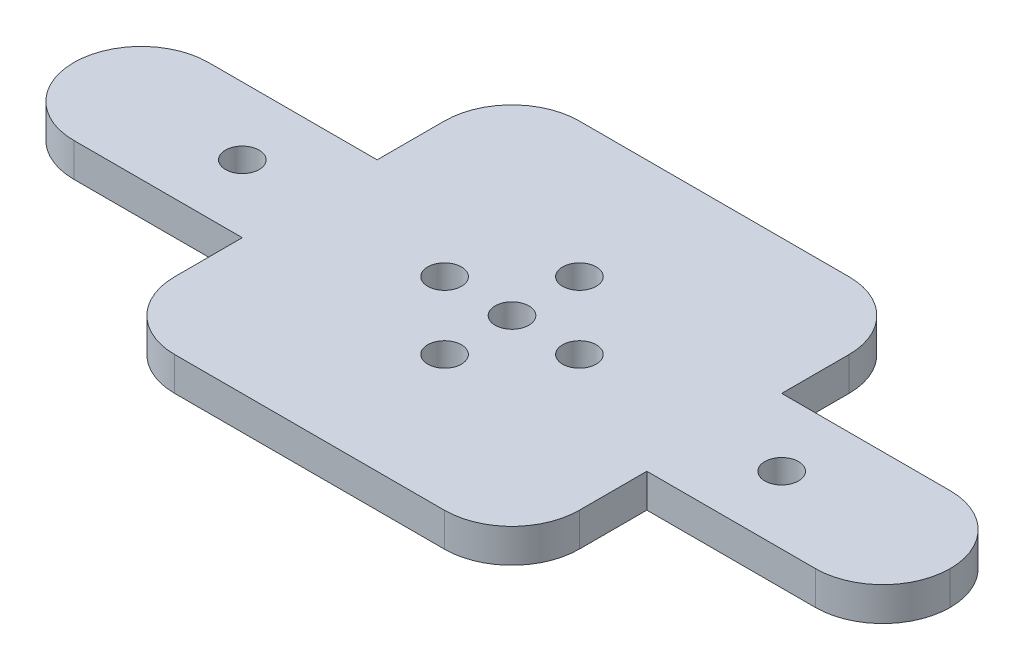
SolidWorks part; units mm, degrees
ref_plane "Front Plane" through (0, 0, 0) normal (0, 0, 1) x (1, 0, 0)
ref_plane "Top Plane" through (0, 0, 0) normal (0, 1, 0) x (1, 0, 0)
ref_plane "Right Plane" through (0, 0, 0) normal (1, 0, 0) x (0, 0, -1)
sketch "Sketch1" plane through (0, 0, 0) normal (0, 1, 0) x (1, 0, 0)
  line L0 (69.4221, 30.0207) -> (-16.2022, 30.0207) construction
  line L1 (0, 0) -> (60, 0)
  line L2 (0, 0) -> (0, 60)
  line L3 (0, 60) -> (60, 60)
  line L4 (60, 0) -> (60, 60)
  line L5 (30, 63.9004) -> (30, -4.8431) construction
  line L6 (23.4653, 40.0207) -> (37.3207, 40.0207) construction
  line L7 (20, 36.8255) -> (20, 23.5223) construction
  line L8 (23.8167, 20.0207) -> (36.7183, 20.0207) construction
  line L9 (40, 25.4802) -> (40, 39.2352) construction
  line L10 (64.811, 30) -> (-8.1915, 30) construction
  circle A0 centre (30, 40.0207) radius 2.5
  circle A1 centre (20, 30.0207) radius 2.5
  circle A2 centre (30, 20.0207) radius 2.5
  circle A3 centre (40, 30.0207) radius 2.5
  circle A4 centre (30, 30.0207) radius 2.5
  dimension "D3" = 5
  dimension "D4" = 5
  dimension "D5" = 5
  dimension "D6" = 5
  dimension "D11" = 5
  dimension "D1" = 60
  dimension "D2" = 60
  dimension "D7" = 10
  dimension "D8" = 10
  dimension "D9" = 10
  dimension "D10" = 10
extrude "Boss-Extrude2" add sketch "Sketch1" along normal blind 5
sketch "Sketch3" plane through (0, 0, 0) normal (0, 1, 0) x (1, 0, 0)
  line L0 (73.9499, 30) -> (-18.7239, 30) construction
  line L1 (30, 64.8678) -> (30, -8.394) construction
  line L2 (32.5, 40.0207) -> (75.2565, 40.0207) construction
  line L3 (75.2565, 40.0207) -> (-19.5638, 40.0207) construction
  line L4 (-35, 20.0207) -> (81.6027, 20.0207) construction
  line L5 (60, 0) -> (60, 60) construction
  line L6 (60, 40.0207) -> (95, 40.0207)
  line L7 (60, 40.0207) -> (60, 20.0207)
  line L8 (60, 20.0207) -> (95, 20.0207)
  line L9 (95, 40.0207) -> (95, 20.0207)
  line L10 (0, 60) -> (0, 0) construction
  line L11 (0, 20.0207) -> (-35, 20.0207)
  line L12 (0, 20.0207) -> (0, 40.0207)
  line L13 (0, 40.0207) -> (-35, 40.0207)
  line L14 (-35, 20.0207) -> (-35, 40.0207)
  circle A0 centre (30, 40.0207) radius 2.5 construction
  dimension "D1" = 35
  dimension "D2" = 35
extrude "Boss-Extrude3" add sketch "Sketch3" along normal blind 5
sketch "Sketch5" plane through (0, 0, 0) normal (0, 1, 0) x (1, 0, 0)
  line L0 (42.5, 30.0207) -> (107.6368, 30.0207) construction
  line L1 (107.6368, 30.0207) -> (-59.7355, 30.0207) construction
  line L2 (60, 40.5295) -> (60, 5.0875) construction
  line L3 (60, 40.0207) -> (60, 60) construction
  line L4 (60, 0) -> (60, 20.0207) construction
  line L5 (0, 40.0207) -> (0, 13.7818) construction
  line L6 (0, 20.0207) -> (0, 0) construction
  circle A0 centre (40, 30.0207) radius 2.5 construction
  circle A1 centre (70, 30.0207) radius 2.5
  circle A2 centre (-10, 30.0207) radius 2.5
  dimension "D2" = 10
  dimension "D3" = 5
  dimension "D4" = 5
  dimension "D1" = 10
extrude "Cut-Extrude1" cut sketch "Sketch5" along normal through all
fillet "Fillet1" radius 10 2 edges at (95, 2.5, -20.0207) (95, 2.5, -40.0207)
fillet "Fillet2" radius 10 2 edges at (-35, 2.5, -20.0207) (-35, 2.5, -40.0207)
fillet "Fillet3" radius 10 4 edges at (60, 2.5, 0) (0, 2.5, 0) (60, 2.5, -60) (0, 2.5, -60)
